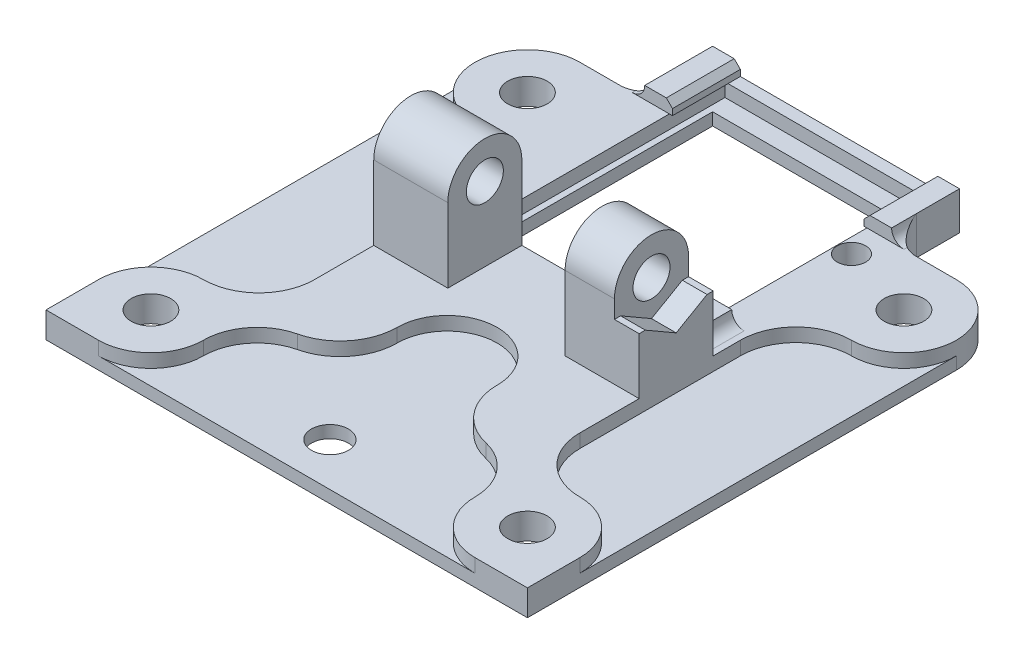
SolidWorks part; units mm, degrees
ref_plane "Front Plane" through (0, 0, 0) normal (0, 0, 1) x (1, 0, 0)
ref_plane "Top Plane" through (0, 0, 0) normal (0, 1, 0) x (1, 0, 0)
ref_plane "Right Plane" through (0, 0, 0) normal (1, 0, 0) x (0, 0, -1)
sketch "Sketch1" plane through (0, 0, 0) normal (0, 1, 0) x (1, 0, 0)
  line L0 (-19.5, 35.2) -> (-19.5, -19.5) construction
  line L1 (-19.5, 19.5) -> (19.5, 19.5)
  line L2 (-19.5, 19.5) -> (-19.5, -19.5)
  line L3 (-19.5, -19.5) -> (19.5, -19.5)
  line L4 (19.5, 19.5) -> (19.5, -19.5)
  line L5 (-19.5, 19.5) -> (19.5, -19.5) construction
  line L6 (-19.5, -19.5) -> (19.5, 19.5) construction
  line L7 (-19.5, -19.5) -> (19.5, -19.5) construction
  line L8 (0, -19.5) -> (0, 19.5) construction
  circle A0 centre (-15.25, -15.25) radius 1.6 construction
  circle A1 centre (15.25, -15.25) radius 1.6 construction
  circle A2 centre (9.2, 17.05) radius 1.15 construction
  circle A3 centre (15.25, 15.25) radius 1.6 construction
  circle A4 centre (-15.25, 15.25) radius 1.6 construction
  circle A5 centre (-15.25, -15.25) radius 1.6
  circle A6 centre (15.25, -15.25) radius 1.6
  circle A7 centre (9.2, 17.05) radius 1.15
  circle A8 centre (15.25, 15.25) radius 1.6
  circle A9 centre (-15.25, 15.25) radius 1.6
  circle A10 centre (-15.25, 15.25) radius 4.25
  circle A11 centre (15.25, 15.25) radius 4.25
  circle A12 centre (-15.25, -15.25) radius 4.25
  circle A13 centre (15.25, -15.25) radius 4.25
  circle A14 centre (0, -16) radius 1.5
  point P0 (0, 0)
  dimension "D1" = 3
  dimension "D2" = 3.5
extrude "Shape" add sketch "Sketch1" along normal blind 2.1 contours A13 L4 A11 L1 A10 L2 A12 L3 A7 | A10 A9 | A11 A8 | A13 A6 | A12 A5 | A12 L2 L3 | A13 L3 L4 region at (-0.0302, 0, -0.0333) region at (-12.3298, 0, -18.1702) region at (18.1702, 0, -18.1702) region at (-18.5507, 0, 18.5507) region at (-15.25, 0, 11.1202) region at (18.1702, 0, 18.1702) region at (18.5507, 0, 18.5507)
sketch "Sketch3" plane through (0, 2.1, 0) normal (0, 1, 0) x (1, 0, 0)
  line L0 (0, 19.5) -> (0, -19.5) construction
  line L1 (-15.25, 19.5) -> (15.25, 19.5) construction
  line L2 (-19.5, -19.5) -> (19.5, -19.5) construction
  line L3 (-19.5, 1.3) -> (19.5, 1.3) construction
  line L4 (-19.5, 15.25) -> (-19.5, -19.5) construction
  line L5 (19.5, 15.25) -> (19.5, -19.5) construction
  line L6 (4.75, 4.3) -> (10.75, 4.3)
  line L7 (-4.75, 4.3) -> (-10.75, 4.3)
  line L8 (-4.75, 4.3) -> (-4.75, -1.7)
  line L9 (-4.75, -1.7) -> (-10.75, -1.7)
  line L10 (-10.75, 4.3) -> (-10.75, -1.7)
  line L11 (-4.75, 4.3) -> (-10.75, -1.7) construction
  line L12 (-4.75, -1.7) -> (-10.75, 4.3) construction
  line L13 (4.75, 4.3) -> (4.75, -1.7)
  line L14 (4.75, -1.7) -> (10.75, -1.7)
  line L15 (10.75, 4.3) -> (10.75, -1.7)
  line L18 (10.75, 4.3) -> (10.75, -1.7)
  point P12 (-7.75, 1.3)
  point P23 (0, 0)
  dimension "D1" = 18.2
  dimension "D2" = 9.5
  dimension "D3" = 6
  dimension "D4" = 6
extrude "Supports" add sketch "Sketch3" along normal blind 9 contours L7 L10 L9 L8 | L15 L6 L13 L14 region at (7.75, 2.1, -1.3) region at (-7.75, 2.1, -1.3)
sketch "Sketch4" plane through (-10.75, 0, 0) normal (-1, 0, 0) x (0, 0, 1)
  line L0 (-1.3, 11.1) -> (-1.3, 2.1) construction
  line L2 (-4.3, 2.1) -> (1.7, 2.1) construction
  line L3 (1.7, 11.1) -> (1.7, 2.1) construction
  line L4 (-4.3, 11.1) -> (1.7, 11.1) construction
  circle A0 centre (-1.3, 8.1) radius 3
  circle A1 centre (-1.3, 8.1) radius 1.5
  line M2 (1.7, 2.1) -> (1.7, 11.1)
  line M4 (-4.3, 11.1) -> (-4.3, 2.1)
  line M11 (1.7, 11.1) -> (-4.3, 11.1)
  dimension "D1" = 3
extrude "Support cuts" cut sketch "Sketch4" against normal up to surface (21.5 mm away) contours A1 L0 | L0 A1 | A0 M11 M4 | A0 M2 M11 region at (-10.75, 10.4299, 1.0299) region at (-10.75, 10.4299, -3.6299) region at (-10.75, 8.1, -0.6634) region at (-10.75, 8.1, -1.9366) up to face at (10.75, 6.6, -1.3)
sketch "Sketch5" plane through (10.75, 0, 0) normal (1, 0, 0) x (0, 0, -1)
  line L0 (-1.2, 6.6566) -> (-1.7, 6.6566)
  line L1 (1.3, 5.2132) -> (3.8, 6.6566)
  line L2 (3.8, 6.6566) -> (3.8, 9.5434)
  line L3 (3.8, 9.5434) -> (1.3, 10.9868)
  line L4 (1.3, 10.9868) -> (-1.2, 9.5434)
  line L5 (-1.2, 9.5434) -> (-1.2, 6.6566)
  line L6 (-1.2, 6.6566) -> (1.3, 5.2132)
  line L7 (3.8, 6.6566) -> (4.3, 6.6566)
  line L8 (4.3, 2.1) -> (-1.7, 2.1) construction
  line L9 (-1.7, 8.1) -> (-1.7, 2.1) construction
  line L10 (4.3, 8.1) -> (4.3, 2.1) construction
  line L12 (-1.7, 8.1) -> (-1.7, 2.1)
  line L13 (-1.7, 2.1) -> (4.3, 2.1)
  line L14 (4.3, 2.1) -> (4.3, 8.1)
  circle A0 centre (1.3, 8.1) radius 2.5 construction
  arc A2 (4.3, 8.1) -> (-1.7, 8.1) centre (1.3, 8.1) ccw construction
  arc A3 (4.3, 8.1) -> (-1.7, 8.1) centre (1.3, 8.1) ccw
  dimension "D1" = 5
extrude "Nut holder" cut sketch "Sketch5" against normal blind 2 contours L5 L6 L1 L2 L3 L4 | L2 L7 L0 L5 L4 L3 region at (10.75, 6.7313, 1.45) region at (10.75, 8.1, -1.3)
sketch "Sketch6" plane through (-10.75, 0, 0) normal (-1, 0, 0) x (0, 0, 1)
  circle A0 centre (-1.3, 8.1) radius 1.95
  dimension "D1" = 3.9
extrude "Screw cut" cut sketch "Sketch6" against normal offset from surface (3.5 mm away) 18 up to face at (10.75, 5.1485, -1.3)
sketch "Sketch9" plane through (0, 2.1, 0) normal (0, 1, 0) x (1, 0, 0)
  line L0 (8, 4.5) -> (8, 24) construction
  line L1 (8, 24) -> (-8, 24) construction
  line L2 (-8, 24) -> (-8, 4.5) construction
  line L3 (8, 4.5) -> (8, 24)
  line L4 (8, 24) -> (-8, 24)
  line L5 (-8, 24) -> (-8, 4.5)
  line L6 (-15.25, 19.5) -> (15.25, 19.5) construction
  line L7 (-15.25, 19.5) -> (15.25, 19.5)
  line L8 (-8, 24) -> (8, 19.5) construction
  line L9 (-8, 24) -> (8, 24)
  line L14 (10, 25) -> (-10, 25)
  line L15 (10, 25) -> (10, 18.5)
  line L16 (10, 18.5) -> (-10, 18.5)
  line L17 (-10, 25) -> (-10, 18.5)
  line L18 (10, 25) -> (-10, 18.5) construction
  line L19 (10, 18.5) -> (-10, 25) construction
  point P10 (0, 21.75)
  line M5 (15.25, 19.5) -> (-15.25, 19.5)
  dimension "D1" = 1
  dimension "D2" = 2
extrude "Datalogger front" add sketch "Sketch9" against normal up to surface (2.1 mm away) contours L4 L5 L3 M5 | L14 L17 L5 L4 L3 L7 L15 M5 region at (0, 2.1, -21.75) region at (8.2074, 2.1, -21.75) up to face at (0, 0, 17.5)
sketch "Sketch10" plane through (0, 0, -25) normal (0, 0, -1) x (-1, 0, 0)
  line L1 (-8, 2.1) -> (8, 2.1)
  line L2 (-8, 2.1) -> (-8, 1)
  line L3 (-8, 1) -> (8, 1)
  line L4 (8, 2.1) -> (8, 1)
  line L6 (-8, 1) -> (8, 1) construction
  line L8 (8, 2.1) -> (8, 1) construction
extrude "Datalogger main cut" cut sketch "Sketch10" against normal offset from surface (20.7 mm away) 0.2 offset beyond the face yes
sketch "Sketch11" plane through (0, 1, 0) normal (0, 1, 0) x (1, 0, 0)
  line L6 (-7.5, 22.5) -> (7.5, 22.5)
  line L9 (8, 25) -> (-8, 25) construction
  line L12 (-7.5, 4.8) -> (7.5, 4.8)
  line L13 (7.5, 4.8) -> (7.5, 24.5)
  line L14 (7.5, 24.5) -> (-7.5, 24.5)
  line L15 (7.5, 24.5) -> (-7.5, 24.5)
  line L17 (-7.5, 24.5) -> (-7.5, 4.8)
  line L18 (-7.5, 4.8) -> (7.5, 4.8)
  line L19 (7.5, 4.8) -> (7.5, 24.5)
  line L23 (-7.5, 24.5) -> (-7.5, 4.8)
  dimension "D2" = 2.5
  dimension "D1" = 0.5
extrude "Datalogger bottom cut" cut sketch "Sketch11" against normal up to next contours L23 L18 L19 region at (0, 1, -13.65)
sketch "Sketch12" plane through (0, 1, 0) normal (0, 1, 0) x (1, 0, 0)
  line L1 (-8, 25) -> (8, 25)
  line L2 (-8, 25) -> (-8, 24)
  line L3 (-8, 24) -> (8, 24)
  line L4 (8, 25) -> (8, 24)
  dimension "D1" = 1
extrude "Datalogger front retainer" add sketch "Sketch12" along normal up to surface (1.1 mm away) up to face at (0, 2.1, -8.6482)
sketch "Sketch13" plane through (0, 2.1, 0) normal (0, 1, 0) x (1, 0, 0)
  line L1 (-8, 4.3) -> (-9.25, 4.3)
  line L2 (-8, 4.3) -> (-8, 7.3)
  line L3 (-8, 7.3) -> (-9.25, 7.3)
  line L4 (-9.25, 4.3) -> (-9.25, 7.3)
  line L5 (-8, 7.3) -> (-7.75, 7.3)
  line L6 (-8, 7.3) -> (-8, 4.3)
  line L7 (-8, 4.3) -> (-7.75, 4.3)
  line L8 (-7.75, 7.3) -> (-7.75, 4.3)
  line L9 (0, 7.608) -> (0, -4.6396) construction
  line L10 (9.25, 4.3) -> (9.25, 7.3)
  line L11 (8, 7.3) -> (9.25, 7.3)
  line L12 (8, 7.3) -> (7.75, 7.3)
  line L13 (7.75, 7.3) -> (7.75, 4.3)
  line L14 (8, 4.3) -> (7.75, 4.3)
  line L15 (8, 4.3) -> (9.25, 4.3)
  line M8 (8, 24) -> (8, 4.3)
  line M9 (8, 4.3) -> (10.75, 4.3)
  line M25 (-10.75, 4.3) -> (-8, 4.3)
  line M26 (-8, 4.3) -> (-8, 24)
  dimension "D1" = 1.5
  dimension "D2" = 3
  dimension "D3" = 0.25
extrude "Datalogger rear retainers" add sketch "Sketch13" along normal blind 1 contours L4 L3 M25 M26 | L8 L5 L7 M26 | L14 L12 L13 M8 | L11 L10 M8 M9 region at (-8.625, 2.1, -5.8) region at (-7.875, 2.1, -5.8) region at (8.625, 2.1, -5.8) region at (7.875, 2.1, -5.8)
sketch "Sketch14" plane through (0, 2.1, 0) normal (0, 1, 0) x (1, 0, 0)
  line L0 (-15.25, 19.5) -> (-10, 19.5) construction
  line L1 (-10, 25) -> (-7.75, 25)
  line L2 (-10, 25) -> (-10, 19.5)
  line L3 (-10, 19.5) -> (-7.75, 19.5)
  line L4 (-7.75, 25) -> (-7.75, 19.5)
  line L5 (-8, 4.3) -> (-8, 24) construction
  line L8 (0, 25) -> (0, -19.5) construction
  line L9 (10, 25) -> (-10, 25) construction
  line L10 (-19.5, -19.5) -> (19.5, -19.5) construction
  line L11 (10, 25) -> (10, 19.5)
  line L12 (10, 25) -> (7.75, 25)
  line L13 (7.75, 25) -> (7.75, 19.5)
  line L14 (10, 19.5) -> (7.75, 19.5)
  line M43 (10, 19.5) -> (10, 25)
  line M45 (10, 25) -> (-10, 25)
  line M46 (8, 24) -> (8, 7.3)
  line M68 (-8, 7.3) -> (-8, 24)
  line M71 (-10, 25) -> (-10, 19.5)
  line M161 (-8, 24) -> (8, 24)
  dimension "D1" = 0.25
extrude "Datalogger side retainers" add sketch "Sketch14" along normal up to surface (1 mm away) contours M45 M161 M46 M43 | M71 M68 M161 | L4 L3 M161 M68 | L14 L13 M46 M161 region at (-8.975, 2.1, -22.3) region at (-7.875, 2.1, -21.75) region at (8.975, 2.1, -22.3) region at (7.875, 2.1, -21.75) up to face at (-8.5, 3.1, -5.8)
sketch "Sketch15" plane through (0, 0, -25) normal (0, 0, -1) x (-1, 0, 0)
  line L0 (-7.75, 2.6) -> (-8.25, 3.1)
  line L2 (-7.75, 3.1) -> (-7.75, 2.1) construction
  line L3 (-8.25, 3.1) -> (-7.75, 3.1)
  line L4 (-7.75, 3.1) -> (-7.75, 2.6)
  line L5 (0, 0) -> (0, 2.1) construction
  line L6 (-7.75, 2.1) -> (7.75, 2.1) construction
  line L7 (8.25, 3.1) -> (7.75, 3.1)
  line L8 (7.75, 3.1) -> (7.75, 2.6)
  line L9 (7.75, 2.6) -> (8.25, 3.1)
  point P4 (0, 0)
  dimension "D1" = 45
extrude "Datalogger side retainer clips" cut sketch "Sketch15" against normal up to next
sketch "Sketch16" plane through (0, 2.1, 0) normal (0, 1, 0) x (1, 0, 0)
  line L0 (-19.5, 15.25) -> (-19.5, -19.5) construction
  line L1 (-15.25, 11) -> (-15.25, -11) construction
  line L2 (0, -2.4485) -> (-4.0515, -2.4485) construction
  line L3 (0, 25) -> (0, -19.5) construction
  line L4 (7.75, 25) -> (-7.75, 25) construction
  line L5 (-19.5, -19.5) -> (19.5, -19.5) construction
  line L6 (-15.25, -11) -> (0, -11) construction
  line L7 (-11, -15.25) -> (0, -15.25) construction
  line L8 (-4.0515, 25) -> (-4.0515, -19.5) construction
  line L9 (-10.75, 4.3) -> (-10.75, -1.7) construction
  line L10 (-10.75, 6.5) -> (-10.75, 19.5) construction
  line L11 (-10, 19.5) -> (-8, 19.5) construction
  line L12 (-19.5, 15.25) -> (-19.5, -15.25)
  line L13 (-10.75, -1.7) -> (-10.75, -11) construction
  line L14 (-10.75, -6.5) -> (0, -6.5) construction
  line L15 (-15.25, 11) -> (-10.75, 11) construction
  line L16 (-10.75, 6.5) -> (-10.75, -6.5)
  line L17 (-4.75, -1.7) -> (-10.75, -1.7) construction
  line L18 (10.75, 6.5) -> (10.75, -6.5)
  line L19 (-15.25, -19.5) -> (15.25, -19.5)
  circle A0 centre (-15.25, 15.25) radius 4.25
  circle A1 centre (-15.25, -15.25) radius 4.25
  arc A2 (-15.25, 19.5) -> (-19.5, 15.25) centre (-15.25, 15.25) ccw construction
  arc A3 (-15.25, 11) -> (-10.75, 6.5) centre (-15.25, 6.5) cw
  arc A4 (-15.25, -11) -> (-10.75, -6.5) centre (-15.25, -6.5) ccw
  arc A5 (-11, -15.25) -> (-7.625, -11) centre (-6.6366, -15.25) cw
  arc A6 (-7.625, -11) -> (-4.0515, -6.5) centre (-8.6716, -6.5) ccw
  arc A7 (-4.0515, -6.5) -> (4.0515, -6.5) centre (0, -6.5) cw
  arc A8 (7.625, -11) -> (4.0515, -6.5) centre (8.6716, -6.5) cw
  arc A9 (11, -15.25) -> (7.625, -11) centre (6.6366, -15.25) ccw
  circle A10 centre (15.25, -15.25) radius 4.25
  arc A11 (15.25, -11) -> (10.75, -6.5) centre (15.25, -6.5) cw
  arc A12 (15.25, 11) -> (10.75, 6.5) centre (15.25, 6.5) ccw
  circle A13 centre (15.25, 15.25) radius 4.25
  point P57 (0, 0)
  point P58 (0, 0)
  point P60 (-10.75, 6.5415)
  line M39 (-19.5, 15.25) -> (-19.5, -19.5)
  line M40 (-19.5, -19.5) -> (19.5, -19.5)
  line M41 (19.5, -19.5) -> (19.5, 15.25)
  circle M45 centre (0, -16) radius 1.5
extrude "Weight cut" cut sketch "Sketch16" against normal offset from surface (1.1 mm away) 1 contours A1 A0 M39 | A10 A9 A8 A7 A6 A5 A1 M40 M45 | A13 L18 A10 M41 region at (-15.4165, 2.1, 0) region at (0, 2.1, 13.2328) region at (15.4165, 2.1, 0) up to face at (15.25, 0, 16.85)
fillet "Fillets" radius 2 2 edges at (10, 1.05, -19.5) (-10, 1.05, -19.5)
fillet "Fillet2" radius 1 4 edges at (10, 2.1, -20.5) (9.25, 2.1, -5.8) (-10, 2.1, -20.5) (-9.25, 2.1, -5.8)
